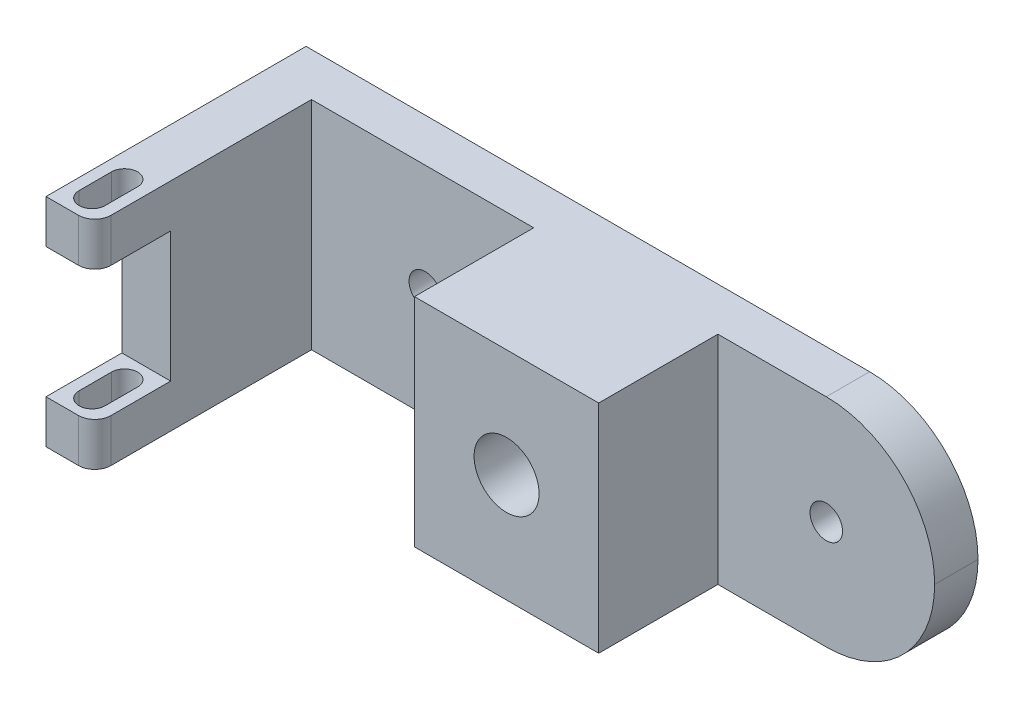
SolidWorks part; units mm, degrees
ref_plane "前视基准面" through (0, 0, 0) normal (0, 0, 1) x (1, 0, 0)
ref_plane "上视基准面" through (0, 0, 0) normal (0, 1, 0) x (1, 0, 0)
ref_plane "右视基准面" through (0, 0, 0) normal (1, 0, 0) x (0, 0, -1)
sketch "草图1" plane through (0, 0, 0) normal (0, 0, 1) x (1, 0, 0)
  line L1 (-28.5, 10) -> (28.5, 10)
  line L2 (-28.5, 10) -> (-28.5, -10)
  line L3 (-28.5, -10) -> (28.5, -10)
  line L4 (28.5, 10) -> (28.5, -10)
  line L5 (-28.5, 10) -> (28.5, -10) construction
  line L6 (-28.5, -10) -> (28.5, 10) construction
  circle A0 centre (-18.5, 0) radius 1.5
  circle A1 centre (18.5, 0) radius 1.5
  point P0 (0, 0)
  dimension "D7" = 3
  dimension "D8" = 3
  dimension "D1" = 57
  dimension "D2" = 20
  dimension "D3" = 18.5
  dimension "D4" = 18.5
  dimension "D5" = 10
  dimension "D6" = 10
extrude "凸台-拉伸1" add sketch "草图1" along normal blind 4
fillet "圆角1" radius 10 2 edges at (28.5, -10, 2) (28.5, 10, 2)
sketch "草图4" plane through (0, 0, 4) normal (0, 0, 1) x (1, 0, 0)
  line L0 (-8.5, 10) -> (8.5, 10)
  line L1 (-8.5, -10) -> (8.5, -10)
  line L2 (-8.5, -10) -> (-8.5, 10)
  line L3 (8.5, -10) -> (8.5, 10)
  line L4 (-28.5, -10) -> (18.5, -10) construction
  point P14 (-8.5, 0)
  point P17 (8.5, 0)
  dimension "D1" = 20
  dimension "D2" = 37
  dimension "D3" = 10
extrude "凸台-拉伸3" add sketch "草图4" along normal blind 11
sketch "草图5" plane through (0, 0, 15) normal (0, 0, 1) x (1, 0, 0)
  circle A0 centre (0, 0) radius 3
  dimension "D1" = 6
extrude "切除-拉伸1" cut sketch "草图5" against normal blind 9
sketch "草图6" plane through (0, 0, 6) normal (0, 0, 1) x (1, 0, 0)
  circle A0 centre (0, 0) radius 1.5
  dimension "D1" = 3
extrude "切除-拉伸2" cut sketch "草图6" against normal up to surface (6 mm away) up to face at (2.5284, 0, 0)
sketch "草图7" plane through (-28.5, 0, 0) normal (-1, 0, 0) x (0, 0, 1)
  line L1 (0, 10) -> (4, 10)
  line L2 (0, 10) -> (0, -10)
  line L3 (0, -10) -> (4, -10)
  line L4 (4, 10) -> (4, -10)
extrude "凸台-拉伸4" add sketch "草图7" along normal blind 5
sketch "草图8" plane through (0, 0, 4) normal (0, 0, 1) x (1, 0, 0)
  line L0 (-33.5, -10) -> (-8.5, -10) construction
  line L1 (-33.5, 10) -> (-29, 10)
  line L2 (-33.5, 10) -> (-33.5, -10)
  line L3 (-33.5, -10) -> (-29, -10)
  line L4 (-29, 10) -> (-29, -10)
  dimension "D1" = 4.5
extrude "凸台-拉伸5" add sketch "草图8" along normal blind 13
sketch "草图9" plane through (0, 0, 17) normal (0, 0, 1) x (1, 0, 0)
  line L0 (-29, -10) -> (-29, 10) construction
  line L1 (-33.5, 10) -> (-29, 10)
  line L2 (-33.5, 10) -> (-33.5, 6)
  line L3 (-33.5, 6) -> (-29, 6)
  line L4 (-29, 10) -> (-29, 6)
  line L5 (-33.5, 10) -> (-33.5, -10) construction
  line L6 (-29, -10) -> (-33.5, -10)
  line L7 (-29, -10) -> (-29, -6)
  line L8 (-29, -6) -> (-33.5, -6)
  line L9 (-33.5, -10) -> (-33.5, -6)
  dimension "D1" = 4
  dimension "D2" = 4
extrude "凸台-拉伸6" add sketch "草图9" along normal blind 7
sketch "草图10" plane through (0, 10, 0) normal (0, 1, 0) x (1, 0, 0)
  line L0 (-31.25, -24) -> (-31.25, 0) construction
  line L1 (-29, -24) -> (-33.5, -24) construction
  line L2 (18.5, 0) -> (-33.5, 0) construction
  line L3 (-31.25, -22) -> (-31.25, -19) construction
  line L4 (-32.45, -22) -> (-32.45, -19)
  line L5 (-30.05, -22) -> (-30.05, -19)
  arc A0 (-32.45, -22) -> (-30.05, -22) centre (-31.25, -22) ccw
  arc A1 (-30.05, -19) -> (-32.45, -19) centre (-31.25, -19) ccw
  point P8 (-31.25, -20.5)
  dimension "D1" = 1.2
  dimension "D2" = 3
  dimension "D3" = 3.5
extrude "切除-拉伸3" cut sketch "草图10" against normal up to surface (20 mm away) up to face at (-8.8, -10, 9.4)
fillet "圆角2" radius 1.5 2 edges at (-29, -8, 24) (-29, 8, 24)
